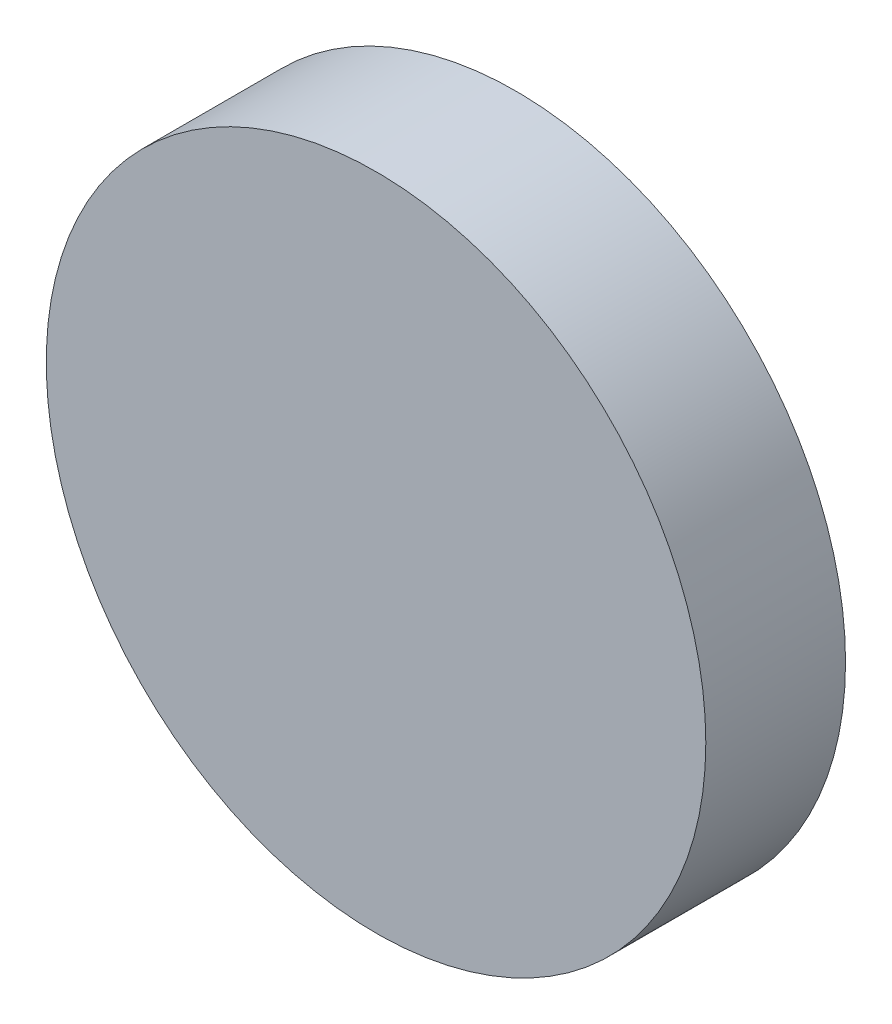
SolidWorks part; units mm, degrees
material "Nichel"
ref_plane "Piano frontale" through (0, 0, 0) normal (0, 0, 1) x (1, 0, 0)
ref_plane "Piano superiore" through (0, 0, 0) normal (0, 1, 0) x (1, 0, 0)
ref_plane "Piano destro" through (0, 0, 0) normal (1, 0, 0) x (0, 0, -1)
sketch "Schizzo1" plane through (0, 0, 0) normal (0, 0, 1) x (1, 0, 0)
  circle A0 centre (0, 0) radius 23.6
  dimension "D1" = 47.2
extrude "Estrusione-Estrusione1" add sketch "Schizzo1" along normal blind 10
